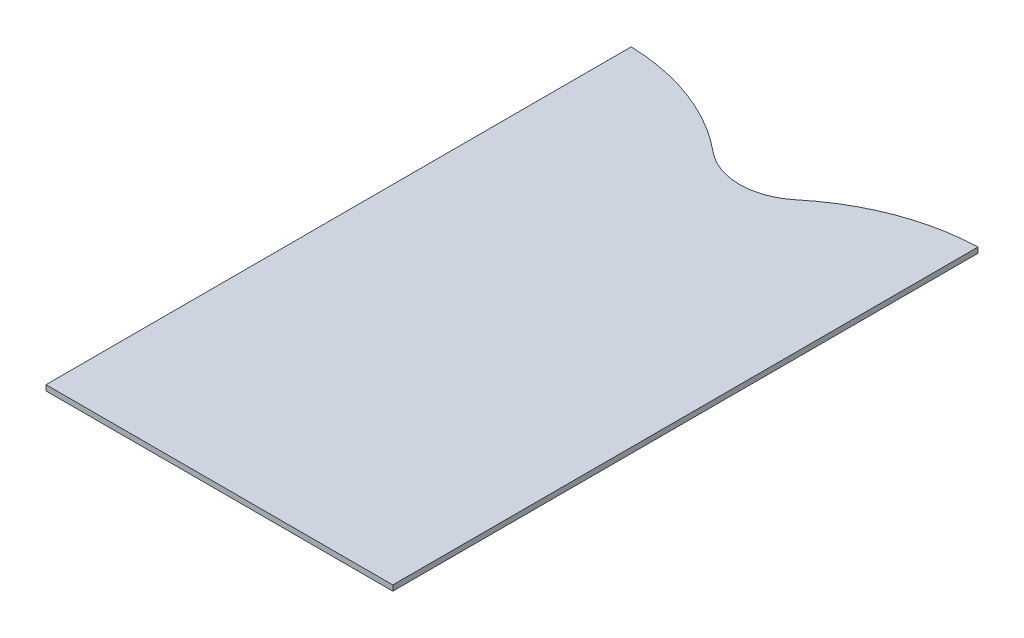
SolidWorks part; units mm, degrees
material "6061-T6 (SS)"
ref_plane "Front Plane" through (0, 0, 0) normal (0, 0, 1) x (1, 0, 0)
ref_plane "Top Plane" through (0, 0, 0) normal (0, 1, 0) x (1, 0, 0)
ref_plane "Right Plane" through (0, 0, 0) normal (1, 0, 0) x (0, 0, -1)
sketch "Sketch1" plane through (0, 0, 0) normal (0, 1, 0) x (1, 0, 0)
  line L1 (-101.6, 171.45) -> (101.6, 171.45)
  line L2 (-101.6, 171.45) -> (-101.6, -171.45)
  line L3 (-101.6, -171.45) -> (101.6, -171.45)
  line L4 (101.6, 171.45) -> (101.6, -171.45)
  line L5 (-101.6, 171.45) -> (101.6, -171.45) construction
  line L6 (-101.6, -171.45) -> (101.6, 171.45) construction
  point P0 (0, 0)
  dimension "D1" = 342.9
  dimension "D2" = 203.2
extrude "Boss-Extrude1" add sketch "Sketch1" along normal blind 3.175
sketch "Sketch2" plane through (0, 3.175, 0) normal (0, 1, 0) x (1, 0, 0)
  line L0 (101.6, 171.45) -> (-101.6, 171.45) construction
  line L1 (101.6, 171.45) -> (38.1, 171.45)
  line L5 (101.6, -171.45) -> (101.6, 171.45)
  line L6 (101.6, 171.45) -> (-101.6, 171.45)
  line L7 (-101.6, 171.45) -> (-101.6, -171.45)
  line L8 (-101.6, -171.45) -> (101.6, -171.45)
  line L9 (101.6, -171.45) -> (101.6, 171.45)
  line L10 (-38.1, 171.45) -> (-101.6, 171.45)
  line L11 (-101.6, 171.45) -> (-101.6, -171.45)
  line L12 (-101.6, -171.45) -> (101.6, -171.45)
  arc A0 (-38.1, 171.45) -> (38.1, 171.45) centre (0, 171.45) ccw
  line M2 (101.6, 171.45) -> (-101.6, 171.45)
  dimension "D1" = 38.1
  dimension "D2" = 0
extrude "Cut-Extrude1" cut sketch "Sketch2" against normal through all contours A0 M2 region at (0, 3.175, -155.2799)
fillet "Fillet1" radius 127 2 edges at (38.1, 1.5875, -171.45) (-38.1, 1.5875, -171.45)
